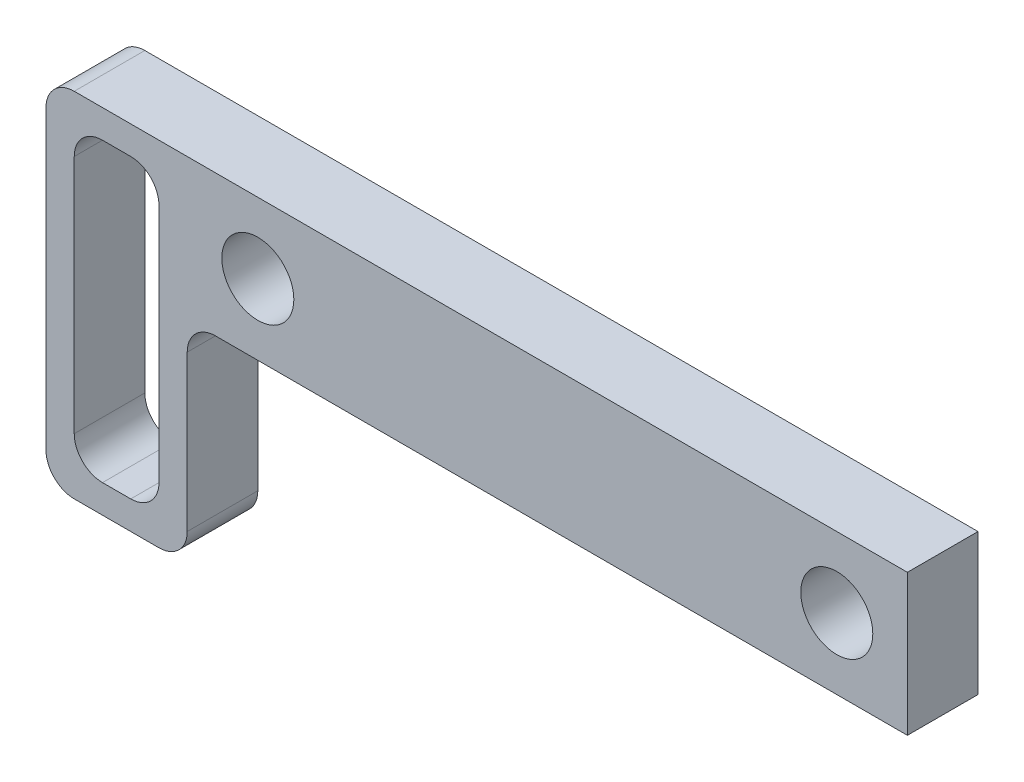
SolidWorks part; units mm, degrees
ref_plane "Front Plane" through (0, 0, 0) normal (0, 0, 1) x (1, 0, 0)
ref_plane "Top Plane" through (0, 0, 0) normal (0, 1, 0) x (1, 0, 0)
ref_plane "Right Plane" through (0, 0, 0) normal (1, 0, 0) x (0, 0, -1)
sketch "Sketch1" plane through (0, 0, 0) normal (0, 0, 1) x (1, 0, 0)
  line L0 (0, 5) -> (51, 5) construction
  line L1 (0, 0) -> (51, 0)
  line L2 (0, 0) -> (0, 10)
  line L3 (0, 10) -> (51, 10)
  line L4 (51, 0) -> (51, 10)
  circle A0 centre (5, 5) radius 2.55
  circle A1 centre (46, 5) radius 2.55
  dimension "D5" = 5.1
  dimension "D1" = 10
  dimension "D2" = 41
  dimension "D3" = 5
  dimension "D4" = 5
extrude "Boss-Extrude1" add sketch "Sketch1" along normal blind 5
sketch "Sketch3" plane through (0, 0, 5) normal (0, 0, 1) x (1, 0, 0)
  line L0 (-2, -13) -> (-8, -13)
  line L1 (0, 10) -> (-10, 10)
  line L2 (0, 10) -> (0, -15)
  line L3 (0, -15) -> (-10, -15)
  line L4 (-10, 10) -> (-10, -15)
  line L5 (-8, 8) -> (-8, -13)
  line L6 (-2, 8) -> (-8, 8)
  line L7 (-2, 8) -> (-2, -13)
  dimension "D1" = 10
  dimension "D2" = 25
  dimension "D3" = 2
extrude "Boss-Extrude2" add sketch "Sketch3" against normal up to surface (5 mm away) up to face at (7.55, 5, 0)
sketch "Sketch5" plane through (51, 0, 0) normal (1, 0, 0) x (0, 0, -1)
  line L1 (0, 0) -> (-25, 0)
  line L2 (0, 0) -> (0, -24)
  line L3 (0, -24) -> (-25, -24)
  line L4 (-25, 0) -> (-25, -24)
  dimension "D1" = 24
  dimension "D2" = 25
extrude "Boss-Extrude3" add sketch "Sketch5" against normal blind 5
fillet "Fillet1" radius 20 1 edges at (46, 0, 2.5)
sketch "Sketch6" plane through (51, 0, 0) normal (1, 0, 0) x (0, 0, -1)
  line L0 (-25, -24) -> (0, -24) construction
  line L1 (-23, -22) -> (-2, -22) construction
  line L2 (-23, -22) -> (-23, -9.5) construction
  line L3 (-23, -9.5) -> (-2, -9.5) construction
  line L4 (-2, -22) -> (-2, -9.5) construction
  line L5 (-25, 0) -> (-25, -24) construction
  circle A0 centre (-23, -9.5) radius 1.75
  circle A1 centre (-23, -22) radius 1.75
  circle A2 centre (-2, -22) radius 1.75
  circle A3 centre (-2, -9.5) radius 1.75
  dimension "D5" = 3.5
  dimension "D1" = 2
  dimension "D2" = 2
  dimension "D3" = 21
  dimension "D4" = 12.5
extrude "Boss-Extrude4" add sketch "Sketch6" along normal blind 3
chamfer "Chamfer1" distance 3 angle 45 4 edges at (51, -9.5, 3.75) (51, -22, 3.75) (51, -22, 24.75) (51, -9.5, 24.75)
hole_wizard "M2x0.4 Tapped Hole1" positions "Sketch7" profile "Sketch8" tap size "M2x0.4" standard "ANSI Metric"
sketch "Sketch7" plane through (54, 0, 0) normal (1, 0, 0) x (0, 0, -1)
  circle A0 centre (-2, -22) radius 1.75 construction
  circle A1 centre (-23, -22) radius 1.75 construction
  circle A2 centre (-23, -9.5) radius 1.75 construction
  circle A3 centre (-2, -9.5) radius 1.75 construction
  point P0 (-23, -22)
  point P2 (-23, -9.5)
  point P4 (-2, -9.5)
  point P6 (-2, -22)
cosmetic thread "Hole Thread1" parameters "D1"=8, "D2"=2
cosmetic thread "Hole Thread2" parameters "D1"=8, "D2"=2
cosmetic thread "Hole Thread3" parameters "D1"=8, "D2"=2
cosmetic thread "Hole Thread4" parameters "D1"=8, "D2"=2
sketch "Sketch8" plane through (54, -22, 23) normal (0, 1, 0) x (0, 0, -1)
  line L0 (0, 0) -> (0, 9.6807)
  line L1 (0, 9.6807) -> (0.8, 9.2)
  line L2 (0.8, 9.2) -> (0.8, 0)
  line L5 (0.8, 0) -> (0, 0)
  line L10 (0, 9.6807) -> (-0.8, 9.2) construction
  line L11 (0, -6.35) -> (0, 107.95) construction
  dimension "Tap Drill Dia." = 1.6
  dimension "Tap Drill Depth" = 9.2
  dimension "Drill Angle" = 118
fillet "Fillet2" radius 2 8 edges at (-8, -13, 2.5) (-2, -13, 2.5) (-8, 8, 2.5) (-2, 8, 2.5) (-10, 10, 2.5) (-10, -15, 2.5) (0, -15, 2.5) (0, 0, 2.5)
sketch "Sketch9" plane through (0, 0, 5) normal (0, 0, 1) x (1, 0, 0)
  line L1 (26, 0) -> (89.2001, 0)
  line L2 (26, 0) -> (26, -37.9343)
  line L3 (26, -37.9343) -> (89.2001, -37.9343)
  line L4 (89.2001, 0) -> (89.2001, -37.9343)
extrude "Cut-Extrude1" cut sketch "Sketch9" against normal through all and the other way through all
